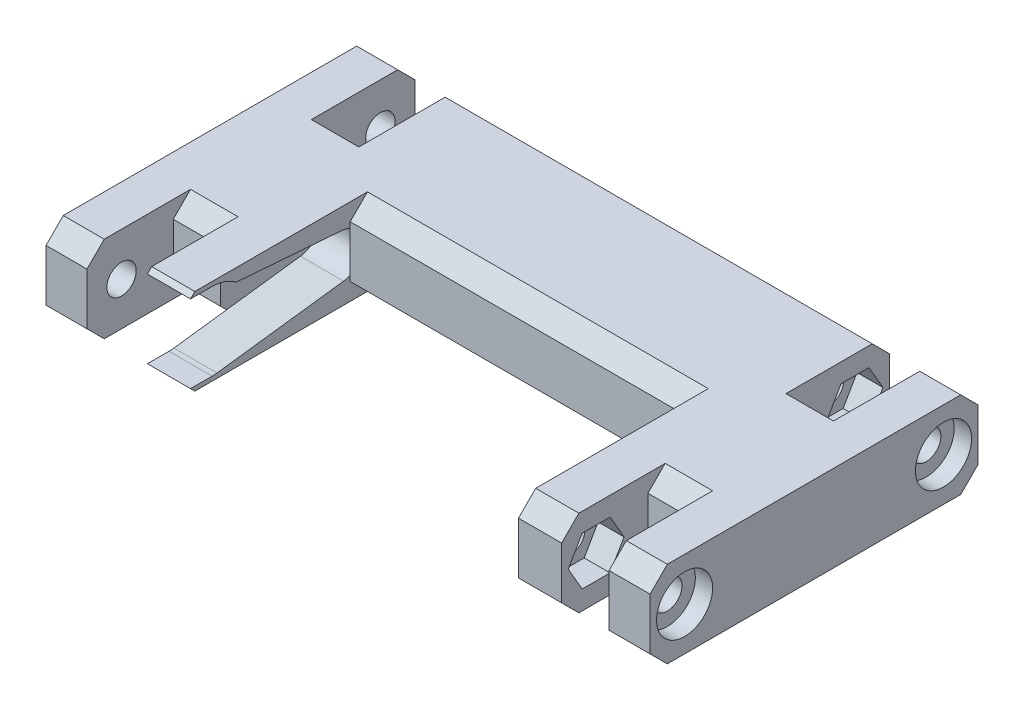
SolidWorks part; units mm, degrees
ref_plane "Front Plane" through (0, 0, 0) normal (0, 0, 1) x (1, 0, 0)
ref_plane "Top Plane" through (0, 0, 0) normal (0, 1, 0) x (1, 0, 0)
ref_plane "Right Plane" through (0, 0, 0) normal (1, 0, 0) x (0, 0, -1)
sketch "Sketch1" plane through (0, 0, 0) normal (0, 1, 0) x (1, 0, 0)
  line L1 (-35, -19) -> (35, -19)
  line L2 (-35, -19) -> (-35, 19)
  line L3 (-35, 19) -> (35, 19)
  line L4 (35, -19) -> (35, 19)
  line L5 (-35, -19) -> (35, 19) construction
  line L6 (-35, 19) -> (35, -19) construction
  point P0 (0, 0)
  dimension "D1" = 70
  dimension "D2" = 38
extrude "Boss-Extrude1" add sketch "Sketch1" along normal blind 10
sketch "Sketch2" plane through (0, 10, 0) normal (0, 1, 0) x (1, 0, 0)
  line L0 (35, 19) -> (-35, 19) construction
  line L1 (-30.25, 19) -> (-24.75, 19)
  line L2 (-30.25, 19) -> (-30.25, 9)
  line L3 (-30.25, 9) -> (-24.75, 9)
  line L4 (-24.75, 19) -> (-24.75, 9)
  line L5 (0, 0) -> (0, 19) construction
  line L6 (24.75, 19) -> (24.75, 9)
  line L7 (30.25, 9) -> (24.75, 9)
  line L8 (30.25, 19) -> (30.25, 9)
  line L9 (30.25, 19) -> (24.75, 19)
  dimension "D1" = 5.5
  dimension "D2" = 10
  dimension "D3" = 49.5
extrude "Cut-Extrude1" cut sketch "Sketch2" against normal through all
hole_wizard "CBORE for M3 Cheese Head Screw1" positions "Sketch7" profile "Sketch8" counterbore size "M3" standard "ISO"
sketch "Sketch7" plane through (35, 0, 0) normal (1, 0, 0) x (0, 0, -1)
  line L0 (-19, 10) -> (19, 10) construction
  line L1 (19, 10) -> (19, 0) construction
  point P0 (15, 5)
  dimension "D1" = 5
  dimension "D2" = 4
sketch "Sketch8" plane through (35, 5, -15) normal (0, 1, 0) x (0, 0, -1)
  line L0 (0, 0) -> (0, 16.0215)
  line L1 (0, 16.0215) -> (1.7, 15)
  line L2 (1.7, 15) -> (1.7, 2)
  line L3 (1.7, 2) -> (3.25, 2)
  line L4 (3.25, 2) -> (3.25, 0)
  line L5 (3.25, 0) -> (0, 0)
  line L10 (0, 16.0215) -> (-1.7, 15) construction
  line L11 (0, -6.35) -> (0, 107.95) construction
  dimension "Hole Dia." = 3.4
  dimension "Hole Depth" = 15
  dimension "C'Bore Dia." = 6.5
  dimension "C'Bore Depth" = 2
  dimension "Drill Angle" = 118
sketch "Sketch9" plane through (24.75, 0, 0) normal (1, 0, 0) x (0, 0, -1)
  line L1 (16.6166, 7.8) -> (13.3834, 7.8)
  line L2 (13.3834, 7.8) -> (11.7668, 5)
  line L3 (11.7668, 5) -> (13.3834, 2.2)
  line L4 (13.3834, 2.2) -> (16.6166, 2.2)
  line L5 (16.6166, 2.2) -> (18.2332, 5)
  line L6 (18.2332, 5) -> (16.6166, 7.8)
  circle A0 centre (15, 5) radius 2.8 construction
  dimension "D1" = 5.6
extrude "Cut-Extrude2" cut sketch "Sketch9" against normal blind 3
mirror "Mirror1" about plane through (0, 0, 0) normal (1, 0, 0) of "Cut-Extrude2", "CBORE for M3 Cheese Head Screw1"
mirror "Mirror2" about plane through (0, 0, 0) normal (0, 0, 1) of "Cut-Extrude1", "CBORE for M3 Cheese Head Screw1", "Cut-Extrude2", "Mirror1"
chamfer "Chamfer1" distance 2 angle 45 12 edges at (32.625, 0, -19) (32.625, 10, -19) (0, 0, -19) (0, 10, -19) (-32.625, 0, -19) (-32.625, 10, -19) (-32.625, 0, 19) (32.625, 0, 19) (0, 0, 19) (32.625, 10, 19) (-32.625, 10, 19) (0, 10, 19)
sketch "Sketch10" plane through (0, 10, 0) normal (0, 1, 0) x (1, 0, 0)
  line L0 (24.75, -19) -> (-24.75, -19) construction
  line L1 (-19.75, -19) -> (19.75, -19)
  line L2 (-19.75, -19) -> (-19.75, 1)
  line L3 (-19.75, 1) -> (19.75, 1)
  line L4 (19.75, -19) -> (19.75, 1)
  line L6 (-24.75, -9) -> (-24.75, -17) construction
  line L7 (24.75, -17) -> (24.75, -9) construction
  dimension "D1" = 5
  dimension "D2" = 20
  dimension "D3" = 5
extrude "Cut-Extrude3" cut sketch "Sketch10" against normal through all
chamfer "Chamfer2" distance 2 angle 45 2 edges at (0, 0, -1) (0, 10, -1)
chamfer "Chamfer3" distance 2 angle 45 8 edges at (27.5, 0, -9) (27.5, 10, -9) (-27.5, 0, 9) (-27.5, 0, -9) (-27.5, 10, 9) (-27.5, 10, -9) (27.5, 0, 9) (27.5, 10, 9)
sketch "Sketch12" plane through (-19.75, 0, 0) normal (1, 0, 0) x (0, 0, -1)
  line L0 (-14.4262, 0.5367) -> (0.2324, 2.4212)
  line L1 (0.0996, 7.5924) -> (-12.2176, 8.5367)
  line L2 (-15, 5) -> (-0.0991, 5) construction
  line L3 (-15, 0.5) -> (-15, 9.5) construction
  line L4 (-15, 9.5) -> (-19, 9.5)
  line L5 (-19, 9.5) -> (-19, 0.5)
  line L6 (-19, 0.5) -> (-15, 0.5)
  line L7 (-19, 8) -> (-19, 2) construction
  line L8 (-19.5, 5) -> (-15, 5) construction
  line L9 (-0.0991, 5) -> (2.5, 5.0667) construction
  circle A0 centre (-15, 5) radius 4.5 construction
  arc A1 (0.2324, 2.4212) -> (0.0996, 7.5924) centre (-0.0991, 5) ccw
  arc A2 (-12.2176, 8.5367) -> (-15, 9.5) centre (-15, 5) ccw
  arc A3 (-14.4262, 0.5367) -> (-15, 0.5) centre (-15, 5) cw
  dimension "D1" = 9
  dimension "D2" = 8
  dimension "D3" = 2.6
  dimension "D4" = 22
extrude "Cut-Extrude5" cut sketch "Sketch12" against normal up to surface (5 mm away) up to face at (-24.75, 5, 15)
